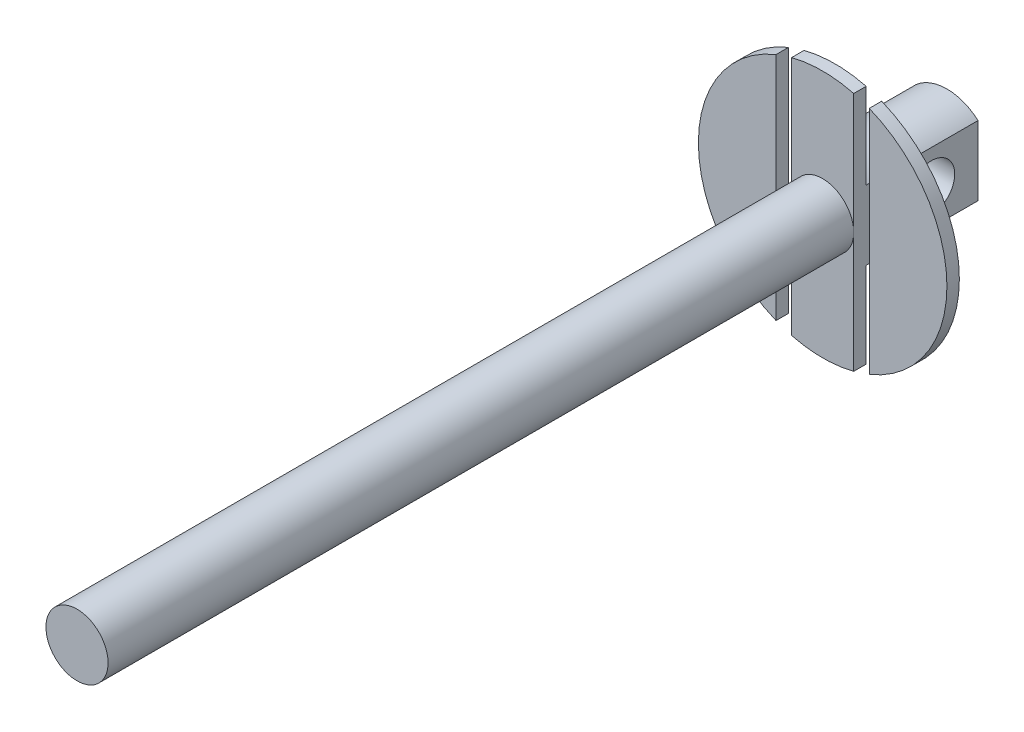
SolidWorks part; units mm, degrees
ref_plane "Front Plane" through (0, 0, 0) normal (0, 0, 1) x (1, 0, 0)
ref_plane "Top Plane" through (0, 0, 0) normal (0, 1, 0) x (1, 0, 0)
ref_plane "Right Plane" through (0, 0, 0) normal (1, 0, 0) x (0, 0, -1)
sketch "Sketch1" plane through (0, 0, 0) normal (0, 0, 1) x (1, 0, 0)
  circle A0 centre (0, 0) radius 25.4
  dimension "D1" = 50.8
extrude "Boss-Extrude1" add sketch "Sketch1" along normal blind 2.54
sketch "Sketch2" plane through (0, 0, 2.54) normal (0, 0, 1) x (1, 0, 0)
  circle A0 centre (0, 0) radius 6.35
  dimension "D1" = 12.7
extrude "Boss-Extrude2" add sketch "Sketch2" along normal blind 152.4
sketch "Sketch3" plane through (0, 0, 0) normal (0, 0, -1) x (-1, 0, 0)
  circle A0 centre (0, 0) radius 9.525
  dimension "D1" = 19.05
extrude "Boss-Extrude3" add sketch "Sketch3" along normal blind 22.86
sketch "Sketch4" plane through (0, 0, 0) normal (0, 1, 0) x (1, 0, 0)
  line L0 (0, -1.397) -> (0, 1.397) construction
  line L1 (9.525, 22.86) -> (6.35, 22.86)
  line L2 (9.525, 22.86) -> (9.525, -2.54)
  line L3 (9.525, -2.54) -> (6.35, -2.54)
  line L4 (6.35, 22.86) -> (6.35, -2.54)
  line L5 (-9.525, 22.86) -> (-6.35, 22.86)
  line L6 (-9.525, 22.86) -> (-9.525, -2.54)
  line L7 (-9.525, -2.54) -> (-6.35, -2.54)
  line L8 (-6.35, 22.86) -> (-6.35, -2.54)
  dimension "D1" = 25.4
  dimension "D2" = 25.4
  dimension "D3" = 6.35
  dimension "D4" = 6.35
extrude "Cut-Extrude2" cut sketch "Sketch4" against normal through all both and the other way through all
sketch "Sketch5" plane through (-6.35, 0, 0) normal (-1, 0, 0) x (0, 0, 1)
  line L0 (1.397, 0) -> (-1.397, 0) construction
  line L1 (-22.86, 7.0995) -> (-22.86, -7.0995) construction
  circle A0 centre (-13.335, 0) radius 4.7625
  dimension "D1" = 9.525
  dimension "D2" = 9.525
extrude "Cut-Extrude3" cut sketch "Sketch5" against normal through all both
equation "\"D2@Sketch4\"=\"D1@Sketch4\""
equation "\"D4@Sketch4\"=\"D3@Sketch4\""
